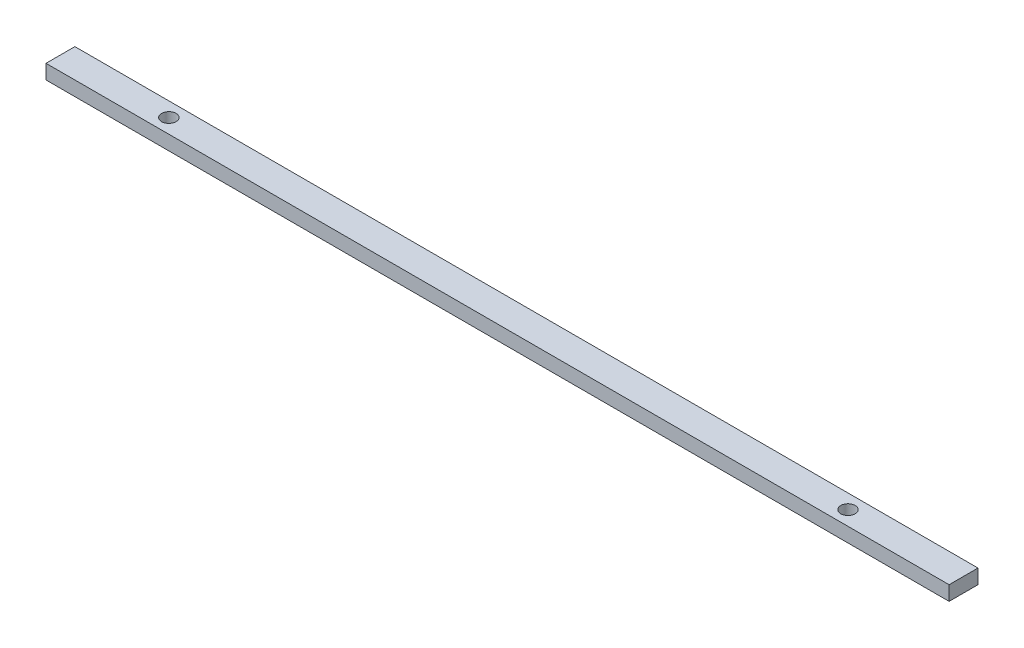
SolidWorks part; units mm, degrees
material "Hexcel AS4C (3000 волосков)"
ref_plane "Front" through (0, 0, 0) normal (0, 0, 1) x (1, 0, 0)
ref_plane "Top" through (0, 0, 0) normal (0, 1, 0) x (1, 0, 0)
ref_plane "Right" through (0, 0, 0) normal (1, 0, 0) x (0, 0, -1)
sketch "Эскиз1" plane through (0, 0, 0) normal (0, 1, 0) x (1, 0, 0)
  line L1 (0, 0) -> (375, 0)
  line L2 (0, 0) -> (0, 12)
  line L3 (0, 12) -> (375, 12)
  line L4 (375, 0) -> (375, 12)
  dimension "D1" = 375
  dimension "D2" = 12
extrude "Бобышка-Вытянуть1" add sketch "Эскиз1" along normal blind 6
sketch "Эскиз2" plane through (0, 6, 0) normal (0, 1, 0) x (1, 0, 0)
  line L0 (0, 0) -> (375, 0) construction
  line L1 (0, 12) -> (0, 0) construction
  circle A0 centre (45, 6) radius 3
  circle A1 centre (327, 6) radius 3
  dimension "D1" = 6
  dimension "D2" = 6
  dimension "D3" = 45
  dimension "D5" = 282
  dimension "D4" = 2
extrude "Вырез-Вытянуть1" cut sketch "Эскиз2" against normal through all
